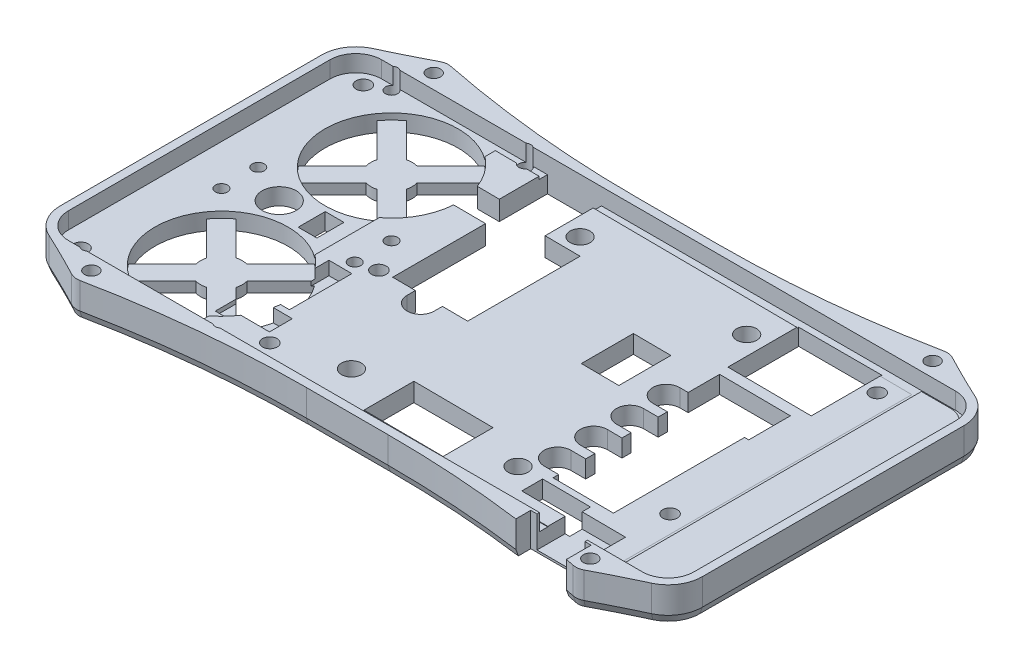
SolidWorks part; units mm, degrees
ref_plane "前视基准面" through (0, 0, 0) normal (0, 0, 1) x (1, 0, 0)
ref_plane "上视基准面" through (0, 0, 0) normal (0, 1, 0) x (1, 0, 0)
ref_plane "右视基准面" through (0, 0, 0) normal (1, 0, 0) x (0, 0, -1)
sketch "草图1" plane through (0, 0, 0) normal (0, 1, 0) x (1, 0, 0)
  line L0 (6, 0.2) -> (143.8, 0.2)
  line L1 (6, 0) -> (143.8, 0) construction
  line L2 (0, -6) -> (0, -68.8) construction
  line L3 (6, -74.8) -> (143.8, -74.8) construction
  line L4 (149.8, -6) -> (149.8, -68.8) construction
  line L5 (150, -6) -> (150, -68.8)
  line L6 (6, -75) -> (143.8, -75)
  line L7 (-0.2, -6) -> (-0.2, -68.8)
  arc A0 (143.8, 0) -> (149.8, -6) centre (143.8, -6) cw construction
  arc A1 (143.8, -74.8) -> (149.8, -68.8) centre (143.8, -68.8) ccw construction
  arc A2 (0, -68.8) -> (6, -74.8) centre (6, -68.8) ccw construction
  arc A3 (6, 0) -> (0, -6) centre (6, -6) ccw construction
  arc A4 (143.8, 0.2) -> (150, -6) centre (143.8, -6) cw
  arc A5 (143.8, -75) -> (150, -68.8) centre (143.8, -68.8) ccw
  arc A6 (-0.2, -68.8) -> (6, -75) centre (6, -68.8) ccw
  arc A7 (6, 0.2) -> (-0.2, -6) centre (6, -6) ccw
  point P7 (149.8, 0)
  point P12 (0, -74.8)
  point P15 (0, 0)
  dimension "D3" = 6
  dimension "D1" = 74.8
  dimension "D2" = 149.8
  dimension "D4" = 0.2
extrude "凸台-拉伸1" add sketch "草图1" along normal blind 4
sketch "草图2" plane through (0, 0, 0) normal (0, -1, 0) x (-1, 0, 0)
  line L0 (-122.6, -55.35) -> (-108.9, -55.35)
  line L1 (-122.6, -69.85) -> (-108.9, -69.85)
  line L2 (-122.6, -69.85) -> (-122.6, -63.95)
  line L3 (-122.6, -63.95) -> (-108.9, -63.95)
  line L4 (-108.9, -69.85) -> (-108.9, -63.95)
  line L5 (-135.3, -1.25) -> (-35.3, -1.25) construction
  line L6 (-135.3, -1.25) -> (-135.3, -73.55) construction
  line L7 (-135.3, -73.55) -> (-35.3, -73.55) construction
  line L8 (-35.3, -1.25) -> (-35.3, -73.55) construction
  line L9 (-108.9, -61.25) -> (-108.9, -55.35)
  line L10 (-122.6, -61.25) -> (-108.9, -61.25)
  line L11 (-122.6, -61.25) -> (-122.6, -55.35)
  line L12 (-122.6, -46.75) -> (-108.9, -46.75)
  line L13 (-108.9, -52.65) -> (-108.9, -46.75)
  line L14 (-122.6, -52.65) -> (-108.9, -52.65)
  line L15 (-122.6, -52.65) -> (-122.6, -46.75)
  line L16 (-122.6, -38.15) -> (-108.9, -38.15)
  line L17 (-108.9, -44.05) -> (-108.9, -38.15)
  line L18 (-122.6, -44.05) -> (-108.9, -44.05)
  line L19 (-122.6, -44.05) -> (-122.6, -38.15)
  line L20 (0, -6) -> (0, -68.8) construction
  line L21 (-35.3, -73.55) -> (-0.8, -73.55) construction
  line L22 (-120.25, -26.65) -> (-111.25, -26.65) construction
  line L23 (-120.25, -26.65) -> (-120.25, -33.15) construction
  line L24 (-120.25, -33.15) -> (-111.25, -33.15) construction
  line L25 (-111.25, -26.65) -> (-111.25, -33.15) construction
  line L26 (-85.8, -48.75) -> (-81.1, -48.75) construction
  line L27 (-85.8, -48.75) -> (-85.8, -58.15) construction
  line L28 (-85.8, -58.15) -> (-81.1, -58.15) construction
  line L29 (-81.1, -48.75) -> (-81.1, -58.15) construction
  line L30 (-71.5, -48.65) -> (-68.2, -48.65) construction
  line L31 (-71.5, -48.65) -> (-71.5, -57.55) construction
  line L32 (-71.5, -57.55) -> (-68.2, -57.55) construction
  line L33 (-68.2, -48.65) -> (-68.2, -57.55) construction
  line L34 (-43.1, -45.05) -> (-38.6, -45.05) construction
  line L35 (-43.1, -45.05) -> (-43.1, -59.05) construction
  line L36 (-43.1, -59.05) -> (-38.6, -59.05) construction
  line L37 (-38.6, -45.05) -> (-38.6, -59.05) construction
  line L38 (-45.3, -61.55) -> (-33.3, -61.55) construction
  line L39 (-45.3, -61.55) -> (-45.3, -66.05) construction
  line L40 (-45.3, -66.05) -> (-33.3, -66.05) construction
  line L41 (-33.3, -61.55) -> (-33.3, -66.05) construction
  line L42 (-0.8, -73.55) -> (-0.8, -1.25) construction
  line L43 (-0.8, -1.25) -> (-35.3, -1.25) construction
  line L44 (-149.8, -6) -> (-149.8, -68.8) construction
  line L45 (-30.8, -34.65) -> (-27.3, -34.65) construction
  line L46 (-30.8, -34.65) -> (-30.8, -40.15) construction
  line L47 (-30.8, -40.15) -> (-27.3, -40.15) construction
  line L48 (-27.3, -34.65) -> (-27.3, -40.15) construction
  line L49 (-120.75, -33.65) -> (-110.75, -33.65)
  line L50 (-110.75, -26.15) -> (-110.75, -33.65)
  line L51 (-120.75, -26.15) -> (-110.75, -26.15)
  line L52 (-120.75, -26.15) -> (-120.75, -33.65)
  line L53 (-86.3, -48.25) -> (-86.3, -58.65)
  line L54 (-86.3, -58.65) -> (-80.6, -58.65)
  line L55 (-80.6, -48.25) -> (-80.6, -58.65)
  line L56 (-86.3, -48.25) -> (-80.6, -48.25)
  line L57 (-72, -48.15) -> (-72, -58.05)
  line L58 (-72, -58.05) -> (-67.7, -58.05)
  line L59 (-67.7, -48.15) -> (-67.7, -58.05)
  line L60 (-72, -48.15) -> (-67.7, -48.15)
  line L61 (-31.3, -34.15) -> (-31.3, -40.65)
  line L62 (-31.3, -40.65) -> (-26.8, -40.65)
  line L63 (-26.8, -34.15) -> (-26.8, -40.65)
  line L64 (-31.3, -34.15) -> (-26.8, -34.15)
  line L65 (-43.6, -44.55) -> (-43.6, -59.55)
  line L66 (-43.6, -59.55) -> (-38.1, -59.55)
  line L67 (-38.1, -44.55) -> (-38.1, -59.55)
  line L68 (-43.6, -44.55) -> (-38.1, -44.55)
  line L69 (-45.8, -61.05) -> (-45.8, -66.55)
  line L70 (-45.8, -66.55) -> (-32.8, -66.55)
  line L71 (-32.8, -61.05) -> (-32.8, -66.55)
  line L72 (-45.8, -61.05) -> (-32.8, -61.05)
  circle A0 centre (-103.2, -9.35) radius 2 construction
  circle A1 centre (-103.2, -64.25) radius 2 construction
  circle A2 centre (-63.2, -64.25) radius 2 construction
  circle A3 centre (-63.2, -9.35) radius 2 construction
  circle A4 centre (-130.8, -5.6) radius 1.25 construction
  circle A5 centre (-131.1, -55.65) radius 1.25 construction
  circle A6 centre (-47.7, -4.85) radius 1.25 construction
  circle A7 centre (-48.1, -68.75) radius 1.25 construction
  circle A8 centre (-22.8, -70.3) radius 1.25 construction
  circle A9 centre (-5.05, -71.05) radius 1.25 construction
  circle A10 centre (-5.05, -3.25) radius 1.25 construction
  circle A11 centre (-19, -37.4) radius 3.6 construction
  circle A12 centre (-103.2, -9.35) radius 2.4
  circle A13 centre (-63.2, -9.35) radius 2.4
  circle A14 centre (-63.2, -64.25) radius 2.4
  circle A15 centre (-103.2, -64.25) radius 2.4
  circle A16 centre (-19, -37.4) radius 4.1
  circle A17 centre (-130.8, -5.6) radius 1.75
  circle A18 centre (-131.1, -55.65) radius 1.75
  circle A19 centre (-48.1, -68.75) radius 1.75
  circle A20 centre (-22.8, -70.3) radius 1.75
  circle A21 centre (-5.05, -71.05) radius 1.75
  circle A22 centre (-5.05, -3.25) radius 1.75
  circle A23 centre (-47.7, -4.85) radius 1.75
  circle A24 centre (-46.11, -40.57) radius 1.25 construction
  circle A25 centre (-46.11, -40.57) radius 1.75
  point P22 (0, -37.4)
  point P23 (-135.3, -37.4)
  point P28 (-115.75, -33.15)
  point P29 (-115.75, -38.15)
  point P30 (-111.25, -29.9)
  point P31 (-108.9, -41.1)
  point P79 (-0.8, -37.4)
  point P81 (-27.3, -37.4)
  dimension "D21" = 4
  dimension "D34" = 2.5
  dimension "D53" = 7.2
  dimension "D1" = 13.7
  dimension "D2" = 5.9
  dimension "D3" = 72.3
  dimension "D4" = 3.7
  dimension "D5" = 12.7
  dimension "D7" = 14.5
  dimension "D8" = 100
  dimension "D9" = 2.7
  dimension "D10" = 9
  dimension "D11" = 6.5
  dimension "D12" = 11.2
  dimension "D13" = 15.4
  dimension "D14" = 9.4
  dimension "D15" = 4.7
  dimension "D16" = 23.1
  dimension "D17" = 3.3
  dimension "D18" = 8.9
  dimension "D19" = 16
  dimension "D20" = 37.4
  dimension "D22" = 8.1
  dimension "D23" = 32.1
  dimension "D24" = 40
  dimension "D25" = 9.3
  dimension "D26" = 14
  dimension "D27" = 4.5
  dimension "D28" = 12
  dimension "D29" = 4.5
  dimension "D30" = 3.3
  dimension "D31" = 2
  dimension "D32" = 7.5
  dimension "D33" = 14.5
  dimension "D35" = 34.5
  dimension "D36" = 2
  dimension "D37" = 4.25
  dimension "D38" = 2.5
  dimension "D39" = 3.25
  dimension "D40" = 22
  dimension "D41" = 4.8
  dimension "D42" = 12.8
  dimension "D43" = 3.6
  dimension "D44" = 12.4
  dimension "D45" = 4.35
  dimension "D46" = 4.5
  dimension "D47" = 4.2
  dimension "D48" = 17.9
  dimension "D49" = 18.2
  dimension "D50" = 3.5
  dimension "D51" = 5.5
  dimension "D52" = 8.3
  dimension "D58" = 28.18
  dimension "D59" = 1.99
  dimension "D54" = 0.4
  dimension "D55" = 0.5
  dimension "D56" = 0.5
  dimension "D57" = 0.5
  dimension "D6" = 4
sketch "草图7" plane through (0, 0, -0.2) normal (0, 0, -1) x (-1, 0, 0)
  line L0 (-135.3, 4) -> (-35.3, 4.75)
  line L2 (-35.3, 4.75) -> (-35.3, 4)
  line L4 (-35.3, 4) -> (-135.3, 4)
  line L6 (-143.8, 4) -> (-6, 4) construction
  dimension "D1" = 0.75
extrude "凸台-拉伸11" add sketch "草图7" against normal offset from surface (71.2 mm away) 2 from offset 2 up to face at (74.9, 2, 75) offset against normal yes
extrude "切除-拉伸1" cut sketch "草图2" against normal blind 10 contours A12 | A13 | A14 | A15
sketch "草图3" plane through (0, 0, 0) normal (0, 1, 0) x (1, 0, 0)
  line L0 (136.8, -1) -> (136.8, -73.8)
  line L1 (143.8, 0) -> (135.8, 0) construction
  line L2 (149.8, -6) -> (149.8, -68.8) construction
  line L3 (143.8, -74.8) -> (135.8, -74.8) construction
  line L4 (135.8, 0) -> (135.8, -74.8) construction
  line L5 (6, -74.8) -> (143.8, -74.8) construction
  line L6 (135.3, -1.25) -> (135.3, -73.55) construction
  line L7 (143.8, -73.8) -> (136.8, -73.8)
  line L8 (148.8, -6) -> (148.8, -68.8)
  line L9 (143.8, -1) -> (136.8, -1)
  arc A0 (143.8, 0) -> (149.8, -6) centre (143.8, -6) cw construction
  arc A1 (149.8, -68.8) -> (143.8, -74.8) centre (143.8, -68.8) cw construction
  arc A2 (148.8, -68.8) -> (143.8, -73.8) centre (143.8, -68.8) cw
  arc A3 (143.8, -1) -> (148.8, -6) centre (143.8, -6) cw
  point P17 (149.8, 0)
  dimension "D1" = 6
  dimension "D2" = 0.5
extrude "凸台-拉伸9" add sketch "草图3" along normal offset from surface (5 mm away) 1 up to face at (85.3, 4, 37.4) offset beyond the face yes
sketch "草图4" plane through (0, 0, 0) normal (0, 1, 0) x (1, 0, 0)
  line L0 (125.2, -20.85) -> (108.2, -20.85)
  line L1 (108.2, -30.85) -> (109.7, -30.85)
  line L2 (109.7, -30.85) -> (109.7, -62.35)
  line L3 (108.7, -68.85) -> (108.7, -62.35)
  line L4 (49.2, -40.35) -> (49.2, -13.35)
  line L5 (108.2, -30.85) -> (108.2, -20.85)
  line L6 (108.7, -68.85) -> (120.2, -68.85)
  line L7 (108.2, -30.85) -> (125.2, -30.85) construction
  line L8 (109.7, -62.35) -> (124.2, -62.35)
  line L9 (80.466, -18.85) -> (96.6871, -18.85) construction
  line L10 (107.2, 11.628) -> (107.2, 24.7853) construction
  line L11 (49.2, -13.35) -> (67.2, -13.35)
  line L12 (125.2, -30.85) -> (124.2, -30.85)
  line L13 (124.2, -30.85) -> (124.2, -62.35)
  line L14 (124.2, -62.35) -> (120.2, -62.35)
  line L15 (120.2, -62.35) -> (120.2, -68.85)
  line L16 (67.2, -13.35) -> (67.2, -40.35)
  line L17 (67.2, -40.35) -> (49.2, -40.35)
  line L18 (63.2, -9.35) -> (46.0308, -9.35) construction
  line L19 (106.2, -55.55) -> (106.2, -28.85) construction
  line L20 (108.7, -63.85) -> (120.2, -63.85)
  line L21 (125.2, -20.85) -> (125.2, -30.85)
  line L22 (106.2, -28.4) -> (108.2, -28.4)
  line L23 (106.2, -34.9) -> (109.7, -34.9)
  line L24 (106.2, -37.1) -> (109.7, -37.1)
  line L25 (109.7, -37.1) -> (109.7, -43.6)
  line L26 (109.7, -43.6) -> (106.2, -43.6)
  line L27 (106.2, -45.8) -> (109.7, -45.8)
  line L28 (106.2, -52.3) -> (109.7, -52.3)
  line L29 (106.2, -54.5) -> (109.7, -54.5)
  line L30 (106.2, -61) -> (109.7, -61)
  line L31 (54.65, -42.35) -> (54.65, -40.35)
  line L32 (61.15, -42.35) -> (61.15, -40.35)
  line L33 (89.5, -35.35) -> (89.5, -22.85)
  line L34 (89.5, -22.85) -> (98.5, -22.85)
  line L35 (98.5, -22.85) -> (98.5, -35.35)
  line L36 (98.5, -35.35) -> (89.5, -35.35)
  line L37 (58.8, -1.85) -> (58.8, -13.85)
  line L38 (58.8, -13.85) -> (45.8, -13.85)
  line L39 (107.7, -18.35) -> (107.7, -1.35)
  line L40 (107.7, -1.35) -> (127.7, -1.35)
  line L41 (127.7, -1.35) -> (127.7, -18.35)
  line L42 (127.7, -18.35) -> (107.7, -18.35)
  line L43 (92.2, -59.25) -> (92.2, -71.25)
  line L44 (92.2, -71.25) -> (73.2, -71.25)
  line L45 (73.2, -71.25) -> (73.2, -59.25)
  line L46 (73.2, -59.25) -> (92.2, -59.25)
  line L47 (45.8, -13.85) -> (45.8, -1.85)
  line L48 (45.8, -1.85) -> (58.8, -1.85)
  line L49 (45.8, -11.35) -> (39.8, -11.35)
  line L50 (39.8, -11.35) -> (39.8, -18.05)
  line L51 (39.8, -18.05) -> (45.8, -18.05)
  line L52 (45.8, -18.05) -> (45.8, -11.35)
  line L53 (45.8, -18.05) -> (49.2, -18.05)
  line L54 (45.8, -1.85) -> (45.8, 0.2)
  line L55 (143.8, 0.2) -> (6, 0.2) construction
  line L56 (45.8, 0.2) -> (58.8, 0.2)
  line L57 (58.8, 0.2) -> (58.8, -1.85)
  circle A0 centre (103.2, -9.35) radius 2.4 construction
  circle A1 centre (103.2, -64.25) radius 2.4 construction
  circle A2 centre (103.2, -64.25) radius 2.4
  circle A3 centre (63.2, -64.25) radius 2.4 construction
  circle A4 centre (63.2, -64.25) radius 2.4
  circle A5 centre (103.2, -9.35) radius 2.4 construction
  circle A6 centre (106.2, -31.65) radius 3.25
  circle A7 centre (106.2, -40.35) radius 3.25
  circle A8 centre (106.2, -49.05) radius 3.25
  circle A9 centre (106.2, -57.75) radius 3.25
  circle A10 centre (63.2, -9.35) radius 2.4 construction
  circle A11 centre (63.2, -9.35) radius 2.4 construction
  circle A12 centre (57.9, -42.35) radius 3.25
  point P30 (67.2, -26.85)
  dimension "D7" = 9.5
  dimension "D30" = 4.5
  dimension "D40" = 6.5
  dimension "D18" = 6.5
  dimension "D21" = 4.5
  dimension "D4" = 11.5
  dimension "D5" = 48
  dimension "D6" = 10
  dimension "D8" = 4
  dimension "D9" = 5
  dimension "D10" = 5
  dimension "D11" = 17
  dimension "D12" = 6.5
  dimension "D13" = 1
  dimension "D14" = 14
  dimension "D15" = 18
  dimension "D16" = 4
  dimension "D17" = 27
  dimension "D19" = 33
  dimension "D20" = 5.3
  dimension "D22" = 4.4
  dimension "D23" = 13
  dimension "D24" = 1.5
  dimension "D25" = 12.5
  dimension "D26" = 5.5
  dimension "D27" = 9
  dimension "D28" = 8.7
  dimension "D29" = 12
  dimension "D31" = 20
  dimension "D32" = 9
  dimension "D33" = 17
  dimension "D34" = 11
  dimension "D35" = 19
  dimension "D36" = 12
  dimension "D37" = 7
  dimension "D38" = 11.5
  dimension "D39" = 22.3
  dimension "D41" = 3
  dimension "D43" = 13.5
  dimension "D44" = 4.7
  dimension "D45" = 6
  dimension "D46" = 2.5
  dimension "D47" = 6.7
  dimension "D42" = 4
extrude "拉伸-薄壁1" add sketch "草图1<2>" along normal blind 8 thin thin type one direction wall 2
sketch "草图1<2>" plane through (0, 0, 0) normal (0, 1, 0) x (1, 0, 0) same geometry as "草图1"
extrude "切除-拉伸2" cut sketch "草图4" along normal through all contours L20 L3 L6 L15 | A9 L30 L2 L29 | A8 L28 L2 L27 | A7 L26 L2 L24 | A6 L23 L2 L1 | A6 L5 L22 | A12 L17 L31 | A12 L32 L17 | L52 L53 L4 L38 | L57 L56 L54 L48 | L41 L42 L39 L40 | L8 L2 L1 L5 L0 L21 L12 L13 | A6 | A7 | A8 | A9 | L46 L43 L44 L45 | L35 L36 L33 L34 | L4 L11 L16 L17 | A12 | L47 L48 L37 L38 | L50 L51 L52 L49 region at (114.45, 0, 66.35) region at (107.7112, 0, 28.6021) region at (108.9903, 0, 33.7511) region at (109.6262, 0, 40.35) region at (107.95, 0, 60.9262) region at (109.6262, 0, 49.05) region at (47.5, 0, 15.95) region at (54.8521, 0, 40.8388) region at (60.9479, 0, 40.8388) region at (52.3, 0, 0.825)
extrude "切除-拉伸3" cut sketch "草图2<11>" against normal through all contours L61 L62 L63 L64 | A16
sketch "草图2<11>" plane through (0, 0, 0) normal (0, -1, 0) x (-1, 0, 0) same geometry as "草图2"
extrude "切除-拉伸4" cut sketch "草图2<13>" against normal through all contours A17 | A18 | A19 | A23 | A22 | A21 | A25
sketch "草图2<13>" plane through (0, 0, 0) normal (0, -1, 0) x (-1, 0, 0) same geometry as "草图2"
extrude "切除-拉伸5" cut sketch "草图2<14>" against normal through all from offset 1.5 contours L67 L66 L65 L68 | L71 L70 L69 L72 offset against normal yes
sketch "草图2<14>" plane through (0, 0, 0) normal (0, -1, 0) x (-1, 0, 0) same geometry as "草图2"
sketch "草图5" plane through (0, 0, 0) normal (0, -1, 0) x (-1, 0, 0)
  text T0 "<b>M3*6</b>" font "@Adobe 黑体 Std R" height 7
  text T1 "<b>M3*6</b>" font "@Adobe 黑体 Std R" height 7
  text T2 "<b>M3*6</b>" font "@Adobe 黑体 Std R" height 7
  text T3 "<b>M3*6</b>" font "@Adobe 黑体 Std R" height 7
extrude "切除-拉伸6" [suppressed] cut sketch "草图5" against normal blind 0.6
sketch "草图6" plane through (0, 0, 0) normal (0, 1, 0) x (1, 0, 0)
  line L1 (0, -6) -> (0, -68.8) construction
  line L2 (149.8, -6) -> (149.8, -68.8) construction
  line L4 (6, 0.2) -> (143.8, 0.2) construction
  line L5 (6, -75) -> (143.8, -75) construction
  circle A0 centre (15, 3.7) radius 1.5 construction
  circle A1 centre (15, -78.5) radius 1.5 construction
  circle A2 centre (134.8, 3.7) radius 1.5 construction
  circle A3 centre (134.8, -78.5) radius 1.5 construction
  circle A4 centre (15, 3.7) radius 3.5
  circle A5 centre (15, -78.5) radius 3.5
  circle A6 centre (134.8, 3.7) radius 3.5
  circle A7 centre (134.8, -78.5) radius 3.5
  circle A8 centre (15, 3.7) radius 1.65
  circle A9 centre (134.8, 3.7) radius 1.65
  circle A10 centre (134.8, -78.5) radius 1.65
  circle A11 centre (15, -78.5) radius 1.65
  dimension "D1" = 3
  dimension "D3" = 0.15
  dimension "D4" = 15
  dimension "D5" = 15
  dimension "D2" = 2
extrude "凸台-拉伸10" add sketch "草图6" along normal up to surface (8 mm away) up to face at (74.9, 8, 37.4)
extrude "切除-拉伸9" cut sketch "草图6<2>" along normal through all contours A8 | A9 | A10 | A11
sketch "草图6<2>" plane through (0, 0, 0) normal (0, 1, 0) x (1, 0, 0) same geometry as "草图6"
fillet "圆角1" radius 250 8 edges at (18.1623, 4, 77) (11.8377, 4, 77) (131.6377, 4, 77) (137.9623, 4, 77) (137.9623, 4, -2.2) (131.6377, 4, -2.2) (11.8377, 4, -2.2) (18.1623, 4, -2.2)
chamfer "倒角1" distance 0.6 angle 70 20 edges at (40.2731, 0, 78.2358) (14.5029, 0, 81.9645) (74.9, 0, 77) (7.988, 0, 78.8506) (109.5269, 0, 78.2358) (-0.9143, 0, 73.2083) (135.2971, 0, 81.9645) (-2.2, 0, 37.4) (141.812, 0, 78.8506) (-0.9143, 0, 1.5917) (150.7143, 0, 73.2083) (7.988, 0, -4.0506) (152, 0, 37.4) (14.5029, 0, -7.1645) (150.7143, 0, 1.5917) (40.2731, 0, -3.4358) (141.812, 0, -4.0506) (74.9, 0, -2.2) (135.2971, 0, -7.1645) (109.5269, 0, -3.4358) first distance on face at (134.8, 0, 80.15)
sketch "草图8" plane through (0, 0, 0) normal (0, -1, 0) x (1, 0, 0)
  line L0 (9.5525, 32.9807) -> (9.5525, 0.9807) construction
  line L1 (9.5525, 0.9807) -> (41.5525, 0.9807) construction
  line L2 (41.5525, 0.9807) -> (41.5525, 32.9807) construction
  line L3 (41.5525, 32.9807) -> (9.5525, 32.9807) construction
  line L4 (31.3, 37.4) -> (26.8, 37.4) construction
  line L7 (41.5525, 41.8193) -> (9.5525, 41.8193) construction
  line L8 (41.5525, 73.8193) -> (41.5525, 41.8193) construction
  line L9 (9.5525, 73.8193) -> (41.5525, 73.8193) construction
  line L10 (9.5525, 41.8193) -> (9.5525, 73.8193) construction
  circle A0 centre (41.5525, 0.9807) radius 1.45
  circle A1 centre (41.5525, 32.9807) radius 1.45
  circle A2 centre (9.5525, 32.9807) radius 1.45
  circle A3 centre (9.5525, 0.9807) radius 1.45
  circle A4 centre (9.5525, 73.8193) radius 1.45
  circle A5 centre (9.5525, 41.8193) radius 1.45
  circle A6 centre (41.5525, 41.8193) radius 1.45
  circle A7 centre (41.5525, 73.8193) radius 1.45
  point P4 (9.5525, 16.9807)
  dimension "D3" = 2.9
  dimension "D4" = 2.9
  dimension "D5" = 2.9
  dimension "D6" = 2.9
  dimension "D1" = 32
  dimension "D2" = 32
extrude "切除-拉伸10" cut sketch "草图8" against normal through all
sketch "草图9" plane through (0, 0, 0) normal (0, -1, 0) x (1, 0, 0)
  line L0 (9.5525, 32.9807) -> (41.5525, 32.9807) construction
  line L1 (41.5525, 32.9807) -> (41.5525, 0.9807) construction
  line L2 (41.5525, 0.9807) -> (9.5525, 0.9807) construction
  line L3 (9.5525, 0.9807) -> (9.5525, 32.9807) construction
  line L4 (9.5525, 32.9807) -> (41.5525, 0.9807) construction
  line L5 (41.5525, 32.9807) -> (9.5525, 0.9807) construction
  line L6 (13.088, 32.9807) -> (41.5525, 4.5163)
  line L7 (41.5525, 4.5163) -> (38.017, 0.9807)
  line L8 (38.017, 0.9807) -> (9.5525, 29.4452)
  line L9 (9.5525, 29.4452) -> (13.088, 32.9807)
  line L10 (38.017, 32.9807) -> (9.5525, 4.5163)
  line L11 (9.5525, 4.5163) -> (13.088, 0.9807)
  line L12 (13.088, 0.9807) -> (41.5525, 29.4452)
  line L13 (41.5525, 29.4452) -> (38.017, 32.9807)
  line L14 (9.5525, 0.9807) -> (41.5525, 0.9807) construction
  line L15 (31.3, 37.4) -> (26.8, 37.4) construction
  line L18 (9.5525, 73.8193) -> (41.5525, 73.8193) construction
  line L19 (9.5525, 41.8193) -> (41.5525, 73.8193) construction
  line L20 (9.5525, 73.8193) -> (9.5525, 41.8193) construction
  line L21 (41.5525, 73.8193) -> (9.5525, 73.8193) construction
  line L22 (41.5525, 41.8193) -> (41.5525, 73.8193) construction
  line L23 (9.5525, 41.8193) -> (41.5525, 41.8193) construction
  line L24 (41.5525, 45.3548) -> (38.017, 41.8193)
  line L25 (13.088, 73.8193) -> (41.5525, 45.3548)
  line L26 (9.5525, 70.2837) -> (13.088, 73.8193)
  line L27 (38.017, 41.8193) -> (9.5525, 70.2837)
  line L28 (9.5525, 45.3548) -> (13.088, 41.8193)
  line L29 (38.017, 73.8193) -> (9.5525, 45.3548)
  line L30 (41.5525, 70.2837) -> (38.017, 73.8193)
  line L31 (13.088, 41.8193) -> (41.5525, 70.2837)
  line L32 (41.5525, 41.8193) -> (9.5525, 73.8193) construction
  circle A0 centre (25.5525, 16.9807) radius 16
  circle A1 centre (25.5525, 16.9807) radius 5
  circle A2 centre (25.5525, 57.8193) radius 5
  circle A3 centre (25.5525, 57.8193) radius 16
  dimension "D2" = 10
  dimension "D4" = 5
extrude "切除-拉伸11" cut sketch "草图9" against normal blind 10 contours A1 L10 A0 L6 | A1 L6 A0 L12 | A1 L12 A0 L8 | A1 L8 A0 L10 | A3 L29 A2 L27 | A3 L25 A2 L29 | A3 L31 A2 L25 | A3 L27 A2 L31 region at (25.5525, 0, 28.2322) region at (14.301, 0, 16.9807) region at (36.804, 0, 16.9807) region at (25.5525, 0, 5.7292) region at (36.804, 0, 57.8193) region at (25.5525, 0, 46.5678) region at (14.301, 0, 57.8193) region at (25.5525, 0, 69.0708)
sketch "草图10" plane through (0, 4, 0) normal (0, 1, 0) x (1, 0, 0)
  circle A0 centre (25.5525, -16.9807) radius 16
  circle A1 centre (25.5525, -57.8193) radius 16
  dimension "D1" = 32
  dimension "D2" = 32
extrude "切除-拉伸12" cut sketch "草图10" against normal mid plane 3
sketch "草图11" plane through (0, 8, 0) normal (0, 1, 0) x (1, 0, 0)
  line L0 (119.1, -85.85) -> (119.1, -65.85)
  line L1 (119.1, -65.85) -> (130.6, -65.85)
  line L2 (130.6, -65.85) -> (130.6, -85.85)
  line L3 (130.6, -85.85) -> (119.1, -85.85)
  line L4 (120.2, -63.85) -> (108.7, -63.85) construction
  circle A0 centre (131.1, -55.65) radius 1.75 construction
  circle A1 centre (131.1, -55.65) radius 1.75 construction
  dimension "D1" = 11.5
  dimension "D2" = 0.5
  dimension "D3" = 2
  dimension "D4" = 20
extrude "切除-拉伸13" cut sketch "草图11" against normal blind 4.5 from surface starting at face at (143.4785, 5, 37.4)
sketch "草图12" plane through (0, 8, 0) normal (0, 1, 0) x (1, 0, 0)
  line L0 (117.6, -75.6) -> (117.6, -88.4406)
  line L1 (117.6, -88.4406) -> (132.1, -88.4406)
  line L2 (132.1, -88.4406) -> (132.1, -75.6)
  line L3 (132.1, -75.6) -> (117.6, -75.6)
  line L4 (42.3942, -75) -> (143.8, -75) construction
  line L5 (119.1, -73) -> (119.1, -75) construction
  line L6 (130.6, -75) -> (130.6, -73) construction
  dimension "D1" = 0.6
  dimension "D2" = 1.5
  dimension "D3" = 1.5
extrude "切除-拉伸14" cut sketch "草图12" against normal through all
sketch "草图13" plane through (0, 0, 75.6) normal (0, 0, 1) x (1, 0, 0)
  line L0 (130.6, 5) -> (130.6, 8)
  line L1 (132.1, 8) -> (117.6, 8) construction
  line L2 (130.6, 8) -> (119.1, 8)
  line L3 (119.1, 8) -> (119.1, 5)
  line L4 (119.1, 5) -> (130.6, 5)
extrude "切除-拉伸15" cut sketch "草图13" against normal up to next
equation "\"D1@草图3\"=\"D3@草图1\""
